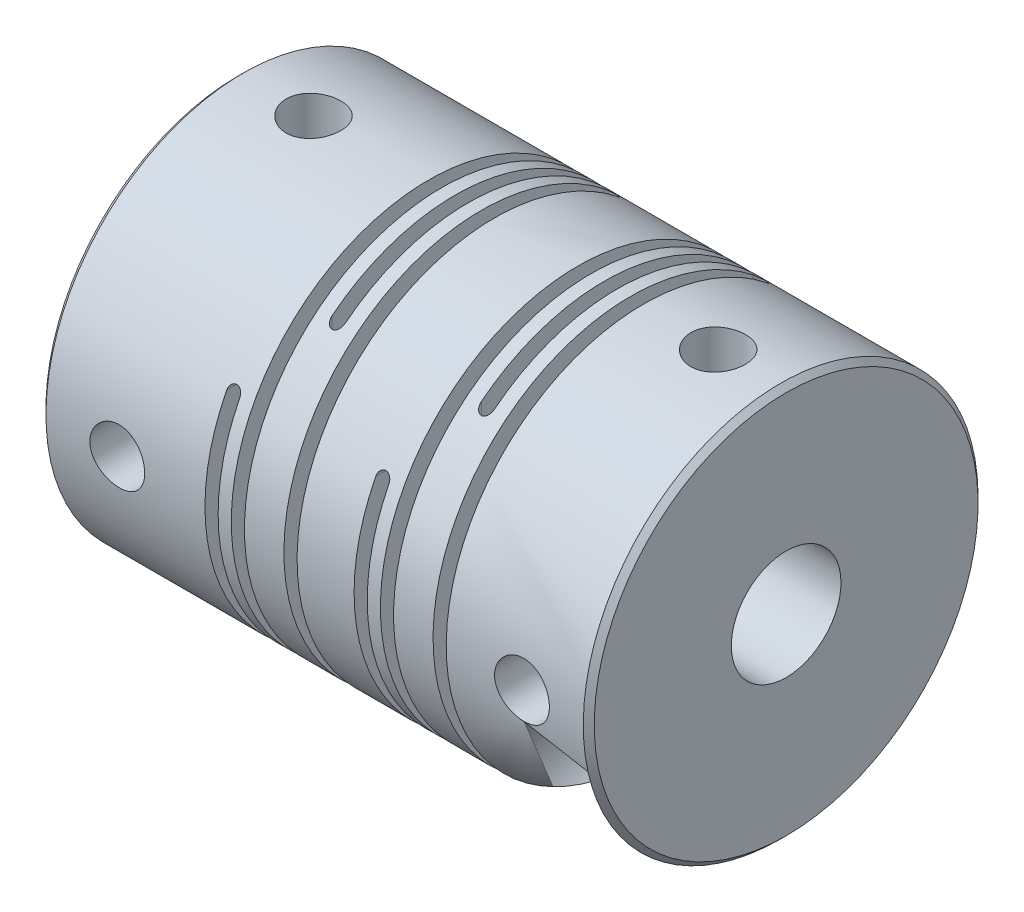
SolidWorks part; units mm, degrees
ref_plane "前视基准面" through (0, 0, 0) normal (0, 0, 1) x (1, 0, 0)
ref_plane "上视基准面" through (0, 0, 0) normal (0, 1, 0) x (1, 0, 0)
ref_plane "右视基准面" through (0, 0, 0) normal (1, 0, 0) x (0, 0, -1)
ref_plane "基准面4" through (0, 0, 0) normal (0, 0, 1) x (1, 0, 0)
sketch "草图1" plane through (0, 0, 0) normal (0, 0, 1) x (1, 0, 0)
  line L0 (0, 10.25) -> (0, 4)
  line L1 (0, 4) -> (6.5, 4)
  line L2 (6.5, 4) -> (6.5, 4.25)
  line L3 (6.5, 4.25) -> (17.5, 4.25)
  line L4 (17.5, 4.25) -> (17.5, 4)
  line L5 (17.5, 4) -> (25, 4)
  line L6 (25, 4) -> (25, 10.25)
  line L7 (25, 10.25) -> (24.75, 10.5)
  line L8 (24.75, 10.5) -> (0.25, 10.5)
  line L9 (0.25, 10.5) -> (0, 10.25)
  line L10 (25, 1.5) -> (-1, 1.5) construction
  dimension "D1" = 6.5
  dimension "D2" = 2.5
  dimension "D3" = 25
  dimension "D4" = 24.5
revolve "旋转1" add sketch "草图1" angle 360 about L10 reverse direction yes
ref_plane "基准面5" through (3.75, 0, 0) normal (1, 0, 0) x (0, 0, -1)
ref_plane "基准面6" through (22.25, 0, 0) normal (1, 0, 0) x (0, 0, -1)
ref_plane "基准面7" through (0, 0, 0) normal (0, 0, 1) x (1, 0, 0)
sketch "草图4" plane through (0, 0, 0) normal (0, 0, 1) x (1, 0, 0)
  line L0 (7.5, -11.5) -> (14.9, -11.5)
  line L1 (14.9, -11.5) -> (14.9, 5.6)
  line L2 (14.3, 5.6) -> (14.3, -10.25)
  line L3 (14.3, -10.25) -> (8.1, -10.25)
  line L4 (8.1, -10.25) -> (8.1, 5.6)
  line L5 (7.5, 5.6) -> (7.5, -11.5)
  arc A0 (14.9, 5.6) -> (14.3, 5.6) centre (14.6, 5.6) ccw
  arc A1 (8.1, 5.6) -> (7.5, 5.6) centre (7.8, 5.6) ccw
extrude "切除-拉伸1" cut sketch "草图4" against normal blind 10.5 and the other way blind 10.5
ref_plane "基准面8" through (0, 0, 0) normal (0, 0, 1) x (1, 0, 0)
sketch "草图5" plane through (0, 0, 0) normal (0, 0, 1) x (1, 0, 0)
  line L0 (8.7, 11.5) -> (8.7, -5.6)
  line L1 (9.3, -5.6) -> (9.3, 10.647)
  line L2 (9.3, 10.647) -> (15.5, 10.647)
  line L3 (15.5, 10.647) -> (15.5, -5.6)
  line L4 (16.1, -5.6) -> (16.1, 11.5)
  line L5 (16.1, 11.5) -> (8.7, 11.5)
  arc A0 (8.7, -5.6) -> (9.3, -5.6) centre (9, -5.6) ccw
  arc A1 (15.5, -5.6) -> (16.1, -5.6) centre (15.8, -5.6) ccw
extrude "切除-拉伸2" cut sketch "草图5" against normal blind 10.5 and the other way blind 10.5
ref_plane "基准面9" through (0, 0, 0) normal (0, 1, 0) x (1, 0, 0)
sketch "草图6" plane through (0, 0, 0) normal (0, 1, 0) x (1, 0, 0)
  line L0 (11.1, -11.5) -> (18.5, -11.5)
  line L1 (18.5, -11.5) -> (18.5, 5.6)
  line L2 (17.9, 5.6) -> (17.9, -10.25)
  line L3 (17.9, -10.25) -> (11.7, -10.25)
  line L4 (11.7, -10.25) -> (11.7, 5.6)
  line L5 (11.1, 5.6) -> (11.1, -11.5)
  arc A0 (18.5, 5.6) -> (17.9, 5.6) centre (18.2, 5.6) ccw
  arc A1 (11.7, 5.6) -> (11.1, 5.6) centre (11.4, 5.6) ccw
extrude "切除-拉伸3" cut sketch "草图6" against normal blind 10.5 and the other way blind 10.5
ref_plane "基准面10" through (0, 0, 0) normal (0, 1, 0) x (1, 0, 0)
sketch "草图7" plane through (0, 0, 0) normal (0, 1, 0) x (1, 0, 0)
  line L0 (9.9, 11.5) -> (9.9, -5.6)
  line L1 (10.5, -5.6) -> (10.5, 10.25)
  line L2 (10.5, 10.25) -> (16.7, 10.25)
  line L3 (16.7, 10.25) -> (16.7, -5.6)
  line L4 (17.3, -5.6) -> (17.3, 11.5)
  line L5 (17.3, 11.5) -> (9.9, 11.5)
  arc A0 (9.9, -5.6) -> (10.5, -5.6) centre (10.2, -5.6) ccw
  arc A1 (16.7, -5.6) -> (17.3, -5.6) centre (17, -5.6) ccw
extrude "切除-拉伸4" cut sketch "草图7" against normal blind 10.5 and the other way blind 10.5
ref_plane "基准面11" through (0, 0, 0) normal (1, 0, 0) x (0, 0, -1)
ref_plane "基准面12" through (0, 0, 9) normal (0, 0, 1) x (1, 0, 0)
hole_wizard "M3 螺纹孔1" positions "3D草图1" profile "草图9" tap size "M3" standard "Iso"
sketch3d "3D草图1"
  point P0 (3.5009, 1.4475, 8.9998)
  point P2 (21.9543, 1.4475, 8.9998)
sketch "草图9" plane through (3.5009, 1.4475, 8.9998) normal (1, 0, 0) x (0, -1, -0.0058)
  line L0 (0, 0) -> (0, 8.2511)
  line L1 (0, 8.2511) -> (1.25, 7.5)
  line L2 (1.25, 7.5) -> (1.25, 0)
  line L5 (1.25, 0) -> (0, 0)
  line L10 (0, 8.2511) -> (-1.25, 7.5) construction
  line L11 (0, -6.35) -> (0, 107.95) construction
  dimension "螺纹孔钻头直径" = 2.5
  dimension "螺纹孔钻头深度" = 7.5
  dimension "导头角度" = 118
cosmetic thread "孔螺蚊线1" parameters "D1"=6, "D2"=3
cosmetic thread "孔螺蚊线2" parameters "D1"=6, "D2"=3
ref_axis "基准轴1" through (6.5, 1.5, 0) along (-1, 0, 0)
pattern_circular "阵列(圆周)1" count 2 over 90 about axis through (6.5, 1.5, 0) along (-1, 0, 0) of "M3 螺纹孔1"
